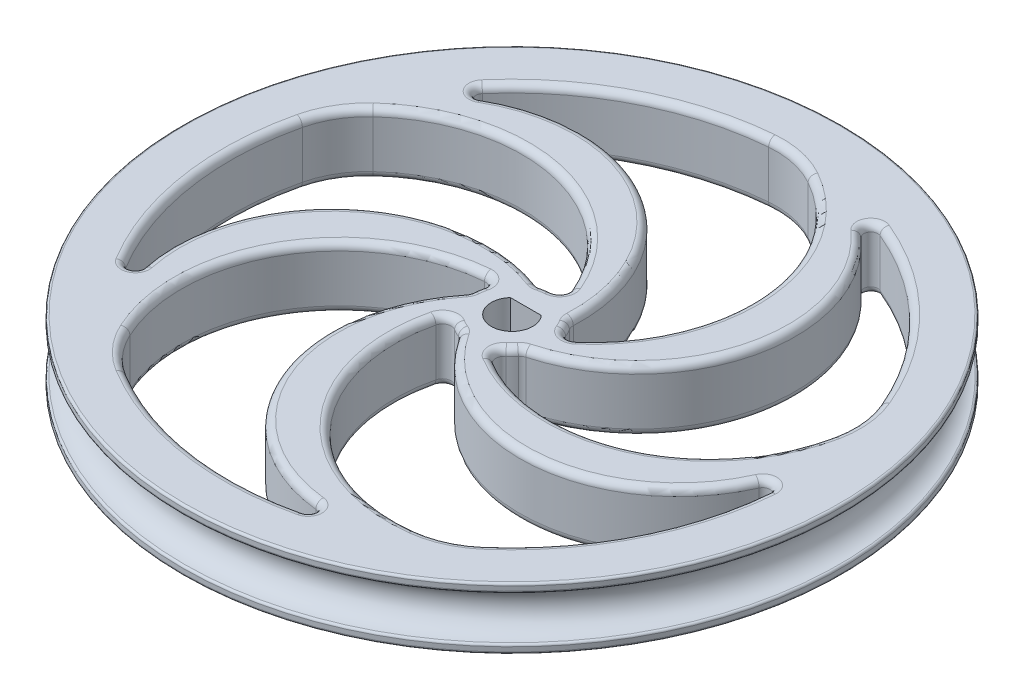
SolidWorks part; units mm, degrees
ref_plane "Front Plane" through (0, 0, 0) normal (0, 0, 1) x (1, 0, 0)
ref_plane "Top Plane" through (0, 0, 0) normal (0, 1, 0) x (1, 0, 0)
ref_plane "Right Plane" through (0, 0, 0) normal (1, 0, 0) x (0, 0, -1)
sketch "Sketch1" plane through (0, 0, 0) normal (0, 0, 1) x (1, 0, 0)
  line L0 (23.8125, 4.445) -> (23.8125, 3.81)
  line L1 (0, 0) -> (23.8125, 0)
  line L2 (0, 0) -> (0, 4.445)
  line L3 (0, 4.445) -> (23.8125, 4.445)
  line L5 (23.8125, 0.635) -> (23.8125, 0)
  arc A0 (23.8125, 3.81) -> (23.8125, 0.635) centre (23.8125, 2.2225) ccw
  dimension "D1" = 1.5875
  dimension "D4" = 180
  dimension "D2" = 4.445
  dimension "D3" = 22.225
revolve "rim revolve" add sketch "Sketch1" angle 360 about L2
fillet "lip bevel" radius 0.1588 4 edges at (0, 0, -23.8125) (0, 0.635, -23.8125) (0, 3.81, -23.8125) (0, 4.445, -23.8125)
sketch "Sketch3" plane through (0, 4.445, 0) normal (0, 1, 0) x (1, 0, 0)
  line L0 (0, 0) -> (0, 29.6275) construction
  line L1 (0, 0) -> (18.2335, 26.0401) construction
  line L2 (1.2287, -0.8604) -> (20.436, 26.5705) construction
  line L3 (2.4575, -1.7207) -> (20.4848, 24.025) construction
  circle A0 centre (0, 0) radius 20.32
  circle A1 centre (0, 0) radius 3
  arc A3 (0, 20.32) -> (1.2287, -0.8604) centre (-3.6668, 9.4815) cw
  arc A4 (2.4575, -1.7207) -> (4.2248, 19.876) centre (-0.3255, 9.3777) ccw
  arc A5 (19.3255, 6.2792) -> (-0.4386, -1.4345) centre (7.8843, 6.4173) cw
  arc A6 (-0.8771, -2.8689) -> (20.2087, 2.124) centre (8.8181, 3.2075) ccw
  arc A7 (11.9438, -16.4392) -> (-1.4998, -0.0262) centre (8.5396, -5.5154) cw
  arc A8 (-2.9995, -0.0524) -> (8.2649, -18.5632) centre (5.7754, -7.3953) ccw
  arc A9 (-11.9438, -16.4392) -> (-0.4884, 1.4183) centre (-2.6066, -9.8259) cw
  arc A10 (-0.9767, 2.8366) -> (-15.1007, -13.5967) centre (-5.2487, -7.778) ccw
  arc A11 (-19.3255, 6.2792) -> (1.198, 0.9027) centre (-10.1505, -0.5574) cw
  arc A12 (2.3959, 1.8054) -> (-17.5976, 10.16) centre (-9.0193, 2.5883) ccw
  circle A13 centre (0, 0) radius 1.5
  point P18 (2.9947, 0.1785)
  point P45 (0, 0)
  dimension "D1" = 35
  dimension "D2" = 6
  dimension "D3" = 40.64
  dimension "D4" = 12
  dimension "D6" = 3
  dimension "D5" = 5
extrude "spokes" cut sketch "Sketch3" against normal through all contours A12 A1 A3 A0 | A5 A0 A4 A1 | A7 A0 A6 A1 | A9 A0 A8 A1 | A11 A0 A10 A1 region at (7.9885, 4.445, 10.2111) region at (12.18, 4.445, -4.4421) region at (-7.2428, 4.445, 10.753) region at (-0.4609, 4.445, -12.9565) region at (-12.4648, 4.445, -3.5654)
fillet "hub fillet" radius 0.635 10 edges at (2.9947, 2.2225, -0.1785) (0.7556, 2.2225, -2.9033) (-0.9767, 2.2225, -2.8366) (-2.5277, 2.2225, -1.6158) (-2.9995, 2.2225, 0.0524) (-0.8771, 2.2225, 2.8689) (-2.3178, 2.2225, 1.9047) (1.0952, 2.2225, 2.7929) (2.4575, 2.2225, 1.7207) (2.3959, 2.2225, -1.8054)
fillet "spokes to rim obtuse fillet" radius 6.35 5 edges at (0, 2.2225, -20.32) (19.3255, 2.2225, -6.2792) (11.9438, 2.2225, 16.4392) (-11.9438, 2.2225, 16.4392) (-19.3255, 2.2225, -6.2792)
fillet "spokes to rim acute fillet" radius 0.508 5 edges at (-15.1007, 2.2225, 13.5967) (8.2649, 2.2225, 18.5632) (20.2087, 2.2225, -2.124) (4.2248, 2.2225, -19.876) (-17.5976, 2.2225, -10.16)
fillet "hub face fillet" radius 0.508 80 edges at (-16.7447, 4.445, 10.7582) (-12.7001, 4.445, -0.905) (-0.9824, 4.445, -2.8742) (-0.4726, 4.445, -2.9625) (0.35, 4.445, -3.2925) (-7.7196, 4.445, -10.6234) (-19.0866, 4.445, -6.3864) (-20.0673, 4.445, 3.1949) (19.8703, 4.445, 1.1388) (9.7426, 4.445, 8.1971) (-0.8946, 4.445, 2.9027) (-1.359, 4.445, 2.6745) (-2.2185, 4.445, 2.458) (0.001, 4.445, 13.132) (11.6876, 4.445, 16.3855) (18.1127, 4.445, 9.2105) (-15.406, 4.445, -12.6007) (-3.0638, 4.445, -12.3582) (2.4299, 4.445, -1.8225) (2.6715, 4.445, -1.3649) (3.2395, 4.445, -0.6846) (7.718, 4.445, -10.6246) (0.1757, 4.445, -20.1259) (-9.2397, 4.445, -18.0978) (7.2233, 4.445, -18.5458) (10.8066, 4.445, -6.7328) (2.4842, 4.445, 1.7478) (2.1237, 4.445, 2.119) (1.6521, 4.445, 2.8694) (12.4896, 4.445, 4.057) (19.1952, 4.445, -6.0522) (14.3568, 4.445, -14.38) (5.0572, 4.445, 19.2496) (-4.7853, 4.445, 11.7989) (-3.0371, 4.445, 0.0462) (-2.9636, 4.445, -0.466) (-3.0232, 4.445, -1.3503) (-12.4889, 4.445, 4.059) (-11.9719, 4.445, 16.179) (-3.1626, 4.445, 20.0724) (-0.9824, 0, -2.8742) (-12.7001, 0, -0.905) (-16.7447, 0, 10.7582) (-20.0673, 0, 3.1949) (-19.0866, 0, -6.3864) (-7.7196, 0, -10.6234) (0.35, 0, -3.2925) (-0.4726, 0, -2.9625) (-0.8946, 0, 2.9027) (9.7426, 0, 8.1971) (19.8703, 0, 1.1388) (18.1127, 0, 9.2105) (11.6876, 0, 16.3855) (0.001, 0, 13.132) (-2.2185, 0, 2.458) (-1.359, 0, 2.6745) (3.2395, 0, -0.6846) (2.6715, 0, -1.3649) (2.4299, 0, -1.8225) (-3.0638, 0, -12.3582) (-15.406, 0, -12.6007) (-9.2397, 0, -18.0978) (0.1757, 0, -20.1259) (7.718, 0, -10.6246) (2.4842, 0, 1.7478) (10.8066, 0, -6.7328) (7.2233, 0, -18.5458) (14.3568, 0, -14.38) (19.1952, 0, -6.0522) (12.4896, 0, 4.057) (1.6521, 0, 2.8694) (2.1237, 0, 2.119) (-3.0371, 0, 0.0462) (-4.7853, 0, 11.7989) (5.0572, 0, 19.2496) (-3.1626, 0, 20.0724) (-11.9719, 0, 16.179) (-12.4889, 0, 4.059) (-3.0232, 0, -1.3503) (-2.9636, 0, -0.466)
sketch "Sketch2" plane through (0, 4.445, 0) normal (0, 1, 0) x (1, 0, 0)
  line L0 (-1.118, 1) -> (1.118, 1)
  circle A0 centre (0, 0) radius 1.5
  dimension "D1" = 3
  dimension "D2" = 2.5
extrude "axle cut" cut sketch "Sketch2" against normal through all contours L0 A0 region at (0, 4.445, 0.148)
